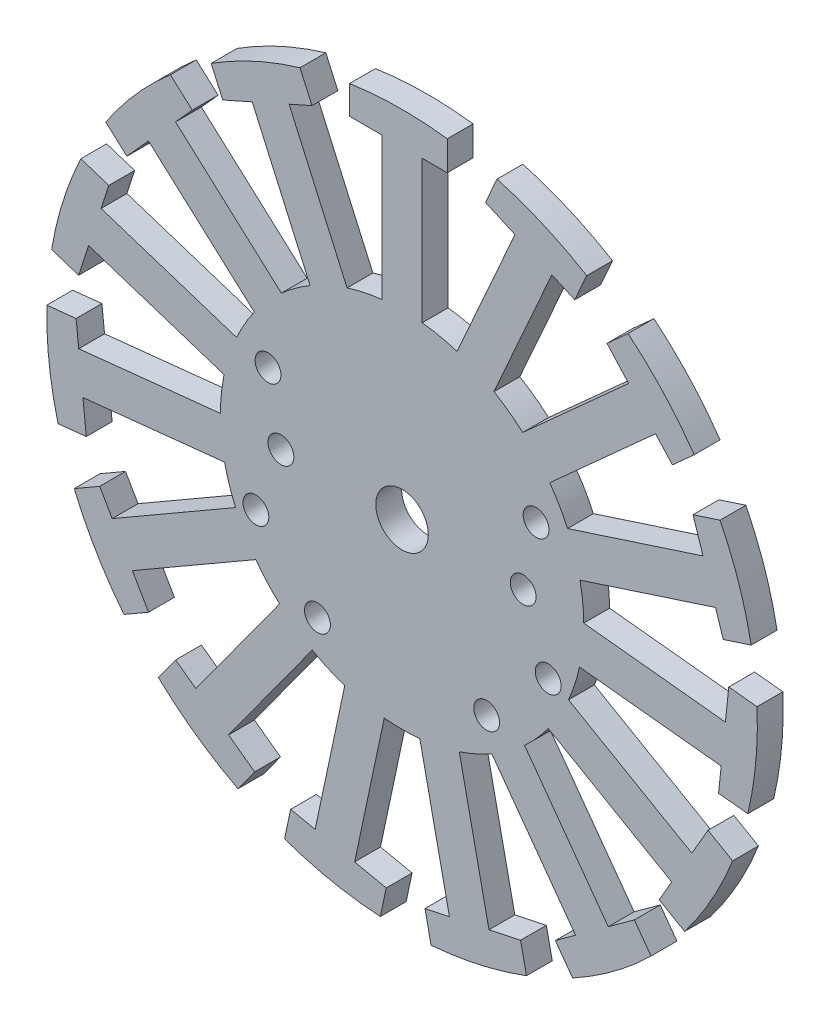
SolidWorks part; units mm, degrees
ref_plane "正面" through (0, 0, 0) normal (0, 0, 1) x (1, 0, 0)
ref_plane "平面" through (0, 0, 0) normal (0, 1, 0) x (1, 0, 0)
ref_plane "右側面" through (0, 0, 0) normal (1, 0, 0) x (0, 0, -1)
sketch "ｽｹｯﾁ1" plane through (0, 0, 0) normal (0, 0, 1) x (1, 0, 0)
  line L0 (0, 0) -> (0, 40)
  line L1 (0, 0) -> (-2.5, 0)
  line L2 (-2.5, 0) -> (-2.5, 40)
  line L3 (0, 0) -> (2.5, 0)
  line L4 (2.5, 0) -> (2.5, 40)
  line L6 (-2.5, 40) -> (-6.5, 40)
  line L7 (2.5, 40) -> (5.6, 40)
  line L8 (5.6, 40) -> (5.6, 43.6422)
  line L9 (-6.5, 40) -> (-6.5, 43.5172)
  arc A1 (5.6, 43.6422) -> (-6.5, 43.5172) centre (0, 0) ccw
  circle A2 centre (0, 0) radius 22.5
  dimension "D2" = 88
  dimension "D3" = 45
  dimension "D4" = 2.5
  dimension "D5" = 2.5
  dimension "D7" = 6.5
  dimension "D8" = 5.6
extrude "ﾎﾞｽ - 押し出し2" add sketch "ｽｹｯﾁ1" along normal blind 3.2 contours L2 A2 L4 L3 L1 | L1 L2 L6 L9 A1 L8 L7 L4 L3 region at (0, -0.8527, 0)
pattern_circular "円形ﾊﾟﾀｰﾝ2" count 15 over 360 about axis through (0, 0, 3.2) along (0, 0, 1) of "ﾎﾞｽ - 押し出し2"
sketch "ｽｹｯﾁ3" plane through (0, 0, 3.2) normal (0, 0, 1) x (1, 0, 0)
  circle A0 centre (0, 0) radius 3.25
  dimension "D1" = 6.5
extrude "ｶｯﾄ - 押し出し2" cut sketch "ｽｹｯﾁ3" against normal blind 3.2
sketch "ｽｹｯﾁ5" plane through (0, 0, 3.2) normal (0, 0, 1) x (1, 0, 0)
  line L0 (-15, 0) -> (15, 0)
  line L1 (0, 0) -> (0, -15.75)
  line L2 (-10.4775, -15.75) -> (10.4775, -15.75)
  circle A0 centre (-15, 0) radius 1.6
  circle A1 centre (15, 0) radius 1.6
  circle A2 centre (10.4775, -15.75) radius 1.6
  circle A3 centre (-10.4775, -15.75) radius 1.6
  point P5 (0, 0)
  point P11 (0, -15.75)
  point P17 (0, 17)
  dimension "D1" = 3.2
  dimension "D4" = 3.2
  dimension "D5" = 3.2
  dimension "D2" = 15.75
  dimension "D3" = 10.4775
extrude "ｶｯﾄ - 押し出し3" cut sketch "ｽｹｯﾁ5" against normal blind 10 contours A0 | A1 | A3 | A2
sketch "ｽｹｯﾁ6" plane through (0, 0, 3.2) normal (0, 0, 1) x (1, 0, 0)
  line L0 (0, 0) -> (-16.6, 0)
  line L1 (-16.6, 0) -> (-16.6, 8)
  line L2 (0, 0) -> (0, 11.5739)
  line L3 (-16.6, 0) -> (-18.1, 0)
  line L4 (-18.1, 0) -> (-18.1, -8)
  circle A0 centre (-15, 0) radius 1.6 construction
  circle A1 centre (-16.6, 8) radius 1.6
  circle A5 centre (-18.1, -8) radius 1.6
  circle A6 centre (18.1, -8) radius 1.6
  circle A7 centre (16.6, 8) radius 1.6
  dimension "D2" = 3.2
  dimension "D5" = 3.2
  dimension "D1" = 8
  dimension "D3" = 1.5
  dimension "D4" = 8
  dimension "D6" = 16.6
extrude "ｶｯﾄ - 押し出し4" cut sketch "ｽｹｯﾁ6" against normal blind 10 contours A1 | A5 | A6 | A7
